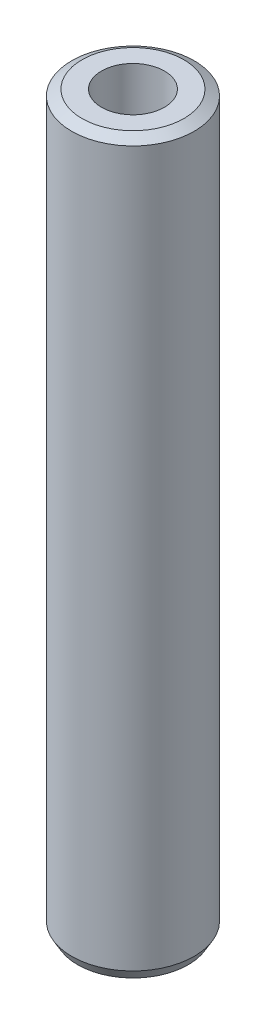
SolidWorks part; units mm, degrees
ref_plane "Front Plane" through (0, 0, 0) normal (0, 0, 1) x (1, 0, 0)
ref_plane "Top Plane" through (0, 0, 0) normal (0, 1, 0) x (1, 0, 0)
ref_plane "Right Plane" through (0, 0, 0) normal (1, 0, 0) x (0, 0, -1)
sketch "Sketch1" plane through (0, 0, 0) normal (0, 1, 0) x (1, 0, 0)
  circle A0 centre (0, 0) radius 12.5
  dimension "SHAFT_OD" = 25
extrude "Boss-Extrude1" add sketch "Sketch1" along normal blind 149.1632
sketch "Sketch2" plane through (0, 0, 0) normal (0, 1, 0) x (1, 0, 0)
  circle A0 centre (0, 0) radius 6.4243
  dimension "BORE_D" = 12.8486
extrude "Cut-Extrude1" cut sketch "Sketch2" along normal through all
chamfer "Chamfer1" distance 1.2115 angle 60 2 edges at (0, 149.1632, 12.5) (0, 0, 12.5) first distance on face at (0, 149.1632, 12.5) first distance on face at (0, 0, 6.4243)
